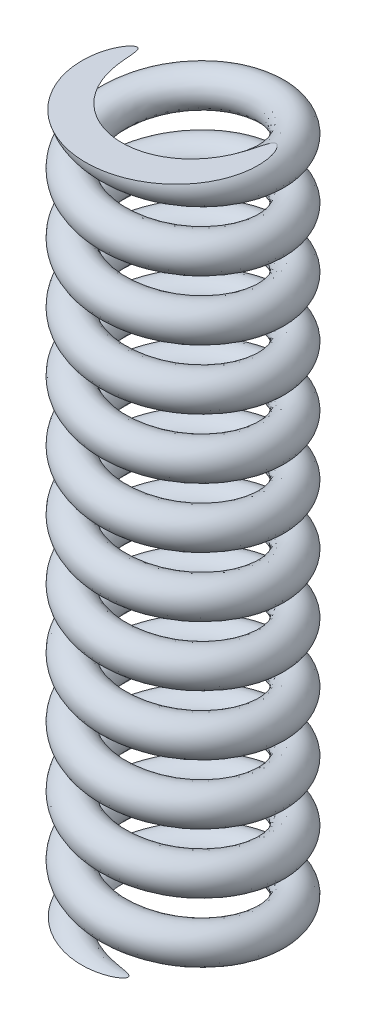
SolidWorks part; units mm, degrees
material "AISI 1035 Acciaio (SS)"
ref_plane "Piano frontale" through (0, 0, 0) normal (0, 0, 1) x (1, 0, 0)
ref_plane "Piano superiore" through (0, 0, 0) normal (0, 1, 0) x (1, 0, 0)
ref_plane "Piano destro" through (0, 0, 0) normal (1, 0, 0) x (0, 0, -1)
sketch "Schizzo1" plane through (0, 0, 0) normal (0, 0, 1) x (1, 0, 0)
  circle A0 centre (-2.25, 0) radius 0.5
  dimension "D1" = 1
  dimension "D2" = 2.25
sketch "Schizzo4" plane through (0, 0, 0) normal (0, 1, 0) x (1, 0, 0)
  circle A0 centre (0, 0) radius 2.25
curve "Elica/Spirale1" pitch 1.7 height 23.8 turns 14
sweep "Sweep1" add profiles "Schizzo1" path "Elica/Spirale1"
sketch "Schizzo5" plane through (0, 0, 0) normal (0, 0, 1) x (1, 0, 0)
  line L0 (0, 0) -> (0, 9.9616) construction
  line L1 (5, 0) -> (-5, 0)
  line L2 (5, 0) -> (5, -5)
  line L3 (5, -5) -> (-5, -5)
  line L4 (-5, 0) -> (-5, -5)
  dimension "D2" = 10
  dimension "D4" = 5
extrude "Taglio-Estrusione2" cut sketch "Schizzo5" against normal through all and the other way through all
ref_plane "Piano1" through (0, 20, 0) normal (0, 1, 0) x (1, 0, 0)
sketch "Schizzo6" plane through (0, 20, 0) normal (0, 1, 0) x (1, 0, 0)
  line L0 (0, 0) -> (-8.1587, 0) construction
  line L1 (3.25, -3.25) -> (-3.25, -3.25)
  line L2 (3.25, -3.25) -> (3.25, 3.25)
  line L3 (3.25, 3.25) -> (-3.25, 3.25)
  line L4 (-3.25, -3.25) -> (-3.25, 3.25)
  line L5 (0, 0) -> (0, -7.2276) construction
  dimension "D1" = 6.5
  dimension "D2" = 6.5
extrude "Taglio-Estrusione3" cut sketch "Schizzo6" along normal through all
sketch "Schizzo7" plane through (0, 20, 0) normal (0, 1, 0) x (1, 0, 0)
  circle A0 centre (0, 0) radius 2.75 construction
  spline S0 degree 3 poles (0.0192, -1.7592) (-0.3409, -1.726) (-0.5144, -1.6848) (-0.8484, -1.554) (-1.0063, -1.465) (-1.2911, -1.2493) (-1.4203, -1.1203) (-1.6364, -0.8366) (-1.7272, -0.6789) (-1.8676, -0.3499) (-1.918, -0.1778) (-1.9829, 0.1766) (-1.9937, 0.3567) (-2.0132, 0.5811) (-2.0176, 0.626) (-2.0292, 0.6926) (-2.0339, 0.7146) (-2.0479, 0.7576) (-2.0569, 0.7789) (-2.0876, 0.8119) (-2.1114, 0.82) (-2.1559, 0.813) (-2.1764, 0.8018) (-2.2316, 0.7632) (-2.2618, 0.7297) (-2.3441, 0.6243) (-2.3862, 0.5466) (-2.4577, 0.384) (-2.4858, 0.2996) (-2.5509, 0.044) (-2.5709, -0.1337) (-2.5688, -0.4862) (-2.5467, -0.6624) (-2.4632, -1.0059) (-2.4028, -1.1706) (-2.2467, -1.4863) (-2.1509, -1.6367) (-1.9333, -1.9116) (-1.8092, -2.0387) (-1.5379, -2.2643) (-1.3924, -2.3618) (-1.0825, -2.5267) (-0.9168, -2.5941) (-0.5805, -2.6929) (-0.4083, -2.7253) (-0.0556, -2.7551) (0.1208, -2.7518) (0.4683, -2.7105) (0.6421, -2.672) (0.9764, -2.5608) (1.1358, -2.489) (1.4394, -2.3129) (1.584, -2.2075) (1.8441, -1.9729) (1.9615, -1.8429) (2.1695, -1.5562) (2.2566, -1.4032) (2.3947, -1.0822) (2.4464, -0.9108) (2.5066, -0.5646) (2.5159, -0.3903) (2.4935, -0.1264) (2.4796, -0.0379) (2.4351, 0.1335) (2.4052, 0.2186) (2.3376, 0.3334) (2.3117, 0.3713) (2.2563, 0.4104) (2.2336, 0.4196) (2.1897, 0.4116) (2.1716, 0.3952) (2.1313, 0.3408) (2.1166, 0.2983) (2.0886, 0.2136) (2.0768, 0.1706) (2.0188, -0.0448) (1.9731, -0.2185) (1.8426, -0.5476) (1.7617, -0.7038) (1.5632, -0.9968) (1.4453, -1.1335) (1.1815, -1.3684) (1.0316, -1.4698) (0.7145, -1.6269) (0.5459, -1.6842) (0.1947, -1.7507) (0.0192, -1.7592) (-0.3409, -1.726) (-0.5144, -1.6848) knots -0.03125 -0.03125 0 0 0.03125 0.03125 0.0625 0.0625 0.09375 0.09375 0.125 0.125 0.15625 0.15625 0.1875 0.1875 0.195312 0.195312 0.199219 0.199219 0.203125 0.203125 0.207031 0.207031 0.210937 0.210937 0.21875 0.21875 0.234375 0.234375 0.25 0.25 0.28125 0.28125 0.3125 0.3125 0.34375 0.34375 0.375 0.375 0.40625 0.40625 0.4375 0.4375 0.46875 0.46875 0.5 0.5 0.53125 0.53125 0.5625 0.5625 0.59375 0.59375 0.625 0.625 0.65625 0.65625 0.6875 0.6875 0.71875 0.71875 0.75 0.75 0.765625 0.765625 0.78125 0.78125 0.789062 0.789062 0.792969 0.792969 0.796875 0.796875 0.804687 0.804687 0.8125 0.8125 0.84375 0.84375 0.875 0.875 0.90625 0.90625 0.9375 0.9375 0.96875 0.96875 1 1 1.03125 1.03125 1.0625 only from (-0.1608, -1.7426) to (-0.1608, -1.7426) construction
